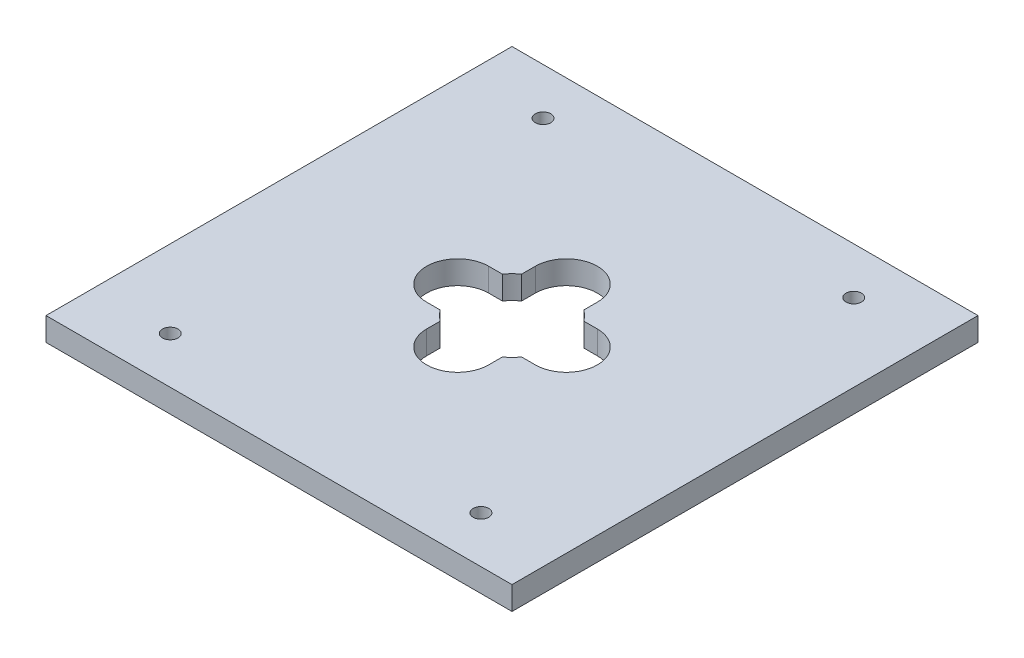
SolidWorks part; units mm, degrees
ref_plane "Front Plane" through (0, 0, 0) normal (0, 0, 1) x (1, 0, 0)
ref_plane "Top Plane" through (0, 0, 0) normal (0, 1, 0) x (1, 0, 0)
ref_plane "Right Plane" through (0, 0, 0) normal (1, 0, 0) x (0, 0, -1)
sketch "Sketch1" plane through (0, 0, 0) normal (0, 1, 0) x (1, 0, 0)
  line L1 (30, -30) -> (-30, -30)
  line L2 (30, -30) -> (30, 30)
  line L3 (30, 30) -> (-30, 30)
  line L4 (-30, -30) -> (-30, 30)
  line L5 (30, -30) -> (-30, 30) construction
  line L6 (30, 30) -> (-30, -30) construction
  point P0 (0, 0)
extrude "Boss-Extrude1" add sketch "Sketch1" along normal blind 3
sketch "Sketch2" plane through (0, 3, 0) normal (0, 1, 0) x (1, 0, 0)
  line L0 (-7, 0) -> (-6.6, 0) construction
  line L1 (-7, 4) -> (-5.2498, 4)
  line L2 (-7, -4) -> (-5.2498, -4)
  line L3 (0, -7) -> (0, -6.6) construction
  line L4 (-4, -7) -> (-4, -5.2498)
  line L5 (4, -7) -> (4, -5.2498)
  line L6 (5.2498, 4) -> (7, 4)
  line L7 (-4, 5.2498) -> (-4, 7)
  line L8 (6.6, 0) -> (7, 0) construction
  line L9 (0, 6.6) -> (0, 7) construction
  line L10 (5.2498, -4) -> (7, -4)
  line L11 (4, 5.2498) -> (4, 7)
  arc A0 (-4, 5.2498) -> (-5.2498, 4) centre (0, 0) ccw
  arc A2 (-7, 4) -> (-7, -4) centre (-7, 0) ccw
  arc A3 (7, -4) -> (7, 4) centre (7, 0) ccw
  arc A4 (-4, -7) -> (4, -7) centre (0, -7) ccw
  arc A5 (4, 7) -> (-4, 7) centre (0, 7) ccw
  arc A6 (5.2498, 4) -> (4, 5.2498) centre (0, 0) ccw
  arc A7 (4, -5.2498) -> (5.2498, -4) centre (0, 0) ccw
  arc A8 (-5.2498, -4) -> (-4, -5.2498) centre (0, 0) ccw
  point P5 (0, 0)
  point P11 (0, 0)
extrude "Cut-Extrude1" cut sketch "Sketch2" against normal through all
sketch "Sketch3" plane through (0, 3, 0) normal (0, 1, 0) x (1, 0, 0)
  circle A0 centre (-20, 24) radius 1
  circle A1 centre (20, 24) radius 1
  circle A2 centre (-20, -24) radius 1
  circle A3 centre (20, -24) radius 1
extrude "Cut-Extrude3" cut sketch "Sketch3" against normal through all
sketch "Sketch4" plane through (0, 0, 0) normal (0, -1, 0) x (1, 0, 0)
  line L0 (-20, 24) -> (20, -24) construction
  line L1 (-20, -24) -> (20, 24) construction
  point P11 (0, 0)
